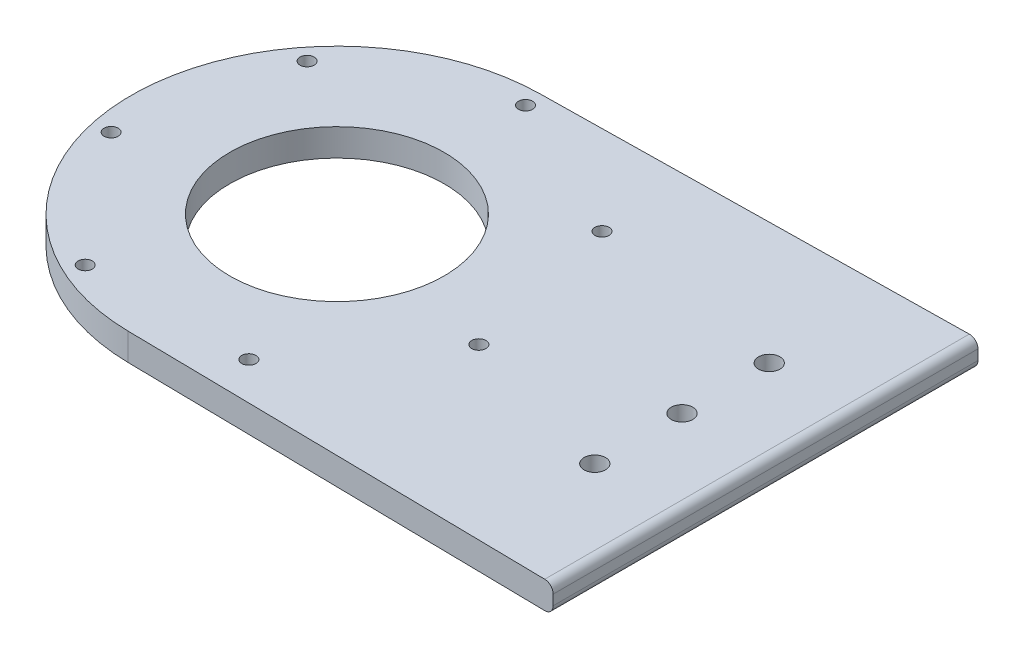
SolidWorks part; units mm, degrees
material "6061 Alloy"
ref_plane "Front Plane" through (0, 0, 0) normal (0, 0, 1) x (1, 0, 0)
ref_plane "Top Plane" through (0, 0, 0) normal (0, 1, 0) x (1, 0, 0)
ref_plane "Right Plane" through (0, 0, 0) normal (1, 0, 0) x (0, 0, -1)
ref_axis "X Axis" through (-88.99, 0, 0) along (1, 0, 0)
ref_axis "Y Axiz" through (0, 0, 55) along (0, 0, -1)
ref_axis "Z Axis" through (0, 55, 0) along (0, -1, 0)
sketch "Sketch1" plane through (0, 0, 0) normal (0, 1, 0) x (1, 0, 0)
  line L0 (0, 0) -> (10, 0) construction
  line L5 (0, 0) -> (100, 0) construction
  line L6 (100, 49.5563) -> (100, -49.5563)
  line L7 (-81.4, 0) -> (81.4, 0) construction
  line L8 (-0.7442, 47.9942) -> (100, 49.5563)
  line L9 (80.5, 20.35) -> (80.5, -20.35) construction
  line L10 (-0.7442, -47.9942) -> (100, -49.5563)
  arc A2 (-0.7442, 47.9942) -> (-0.7442, -47.9942) centre (0, 0) ccw
  circle A8 centre (0, 0) radius 25
  circle A15 centre (80.5, 20.35) radius 0.5
  circle A16 centre (80.5, -20.35) radius 0.5
  circle A19 centre (80.5, 0) radius 0.5
  point P0 (80.5, 20.35)
  point P2 (80.5, -20.35)
  point P29 (0, 0)
  dimension "D2" = 0
  dimension "D3" = 96
  dimension "D5" = 1
  dimension "D7" = 10
  dimension "D9" = 100.7442
  dimension "D10" = 50
  dimension "D13" = 1
  dimension "D14" = 1
  dimension "D4" = 100.7442
  dimension "D8" = 100
  dimension "D11" = 20.35
  dimension "D12" = 19.5
extrude "Boss-Extrude1" add sketch "Sketch1" along normal blind 6.35 contours L8 A2 L10 A8 region at (36.5027, 0, 0)
hole_wizard "M6x1.0 Tapped Hole1" positions "3DSketch1" profile "Sketch2" tap size "M6x1.0" standard "ANSI Metric"
sketch3d "3DSketch1"
  line L0 (80.5, 6.35, -20.35) -> (80.5, 0, -20.35) construction
  line L1 (80.5, 6.35, 0) -> (80.5, 0, 0) construction
  line L2 (80.5, 6.35, 20.35) -> (80.5, 0, 20.35) construction
  point P0 (80.5, 6.35, -20.35)
  point P4 (80.5, 6.35, 0)
  point P8 (80.5, 6.35, 20.35)
sketch "Sketch2" plane through (80.5, 6.35, -20.35) normal (1, 0, 0) x (0, 0, 1)
  line L0 (0, 0) -> (0, 16.5022)
  line L1 (0, 16.5022) -> (2.5, 15)
  line L2 (2.5, 15) -> (2.5, 0)
  line L5 (2.5, 0) -> (0, 0)
  line L10 (0, 16.5022) -> (-2.5, 15) construction
  line L11 (0, -6.35) -> (0, 107.95) construction
  dimension "Tap Drill Dia." = 5
  dimension "Tap Drill Depth" = 15
  dimension "Drill Angle" = 118
cosmetic thread "Hole Thread1" parameters "D1"=12, "D2"=6
cosmetic thread "Hole Thread2" parameters "D1"=12, "D2"=6
cosmetic thread "Hole Thread3" parameters "D1"=12, "D2"=6
sketch "Sketch3" plane through (0, 6.35, 0) normal (0, 1, 0) x (1, 0, 0)
  line L0 (0, 0) -> (0, 44) construction
  circle A0 centre (0, 44) radius 1.5
  circle A1 centre (34.4006, 27.4336) radius 1.5
  circle A2 centre (42.8968, -9.7909) radius 1.5
  circle A3 centre (19.0909, -39.6426) radius 1.5
  circle A4 centre (-19.0909, -39.6426) radius 1.5
  circle A5 centre (-42.8968, -9.7909) radius 1.5
  circle A6 centre (-34.4006, 27.4336) radius 1.5
  point P1 (0, 44)
  point P7 (34.4006, 27.4336)
  point P9 (42.8968, -9.7909)
  point P11 (19.0909, -39.6426)
  point P13 (-19.0909, -39.6426)
  point P15 (-42.8968, -9.7909)
  point P17 (-34.4006, 27.4336)
  dimension "D1" = 44
  dimension "D2" = 3
  dimension "D3" = 7
hole_wizard "M4x0.7 Tapped Hole1" positions "Sketch3" profile "Sketch4" tap size "M4x0.7" standard "ANSI Metric"
sketch "Sketch4" plane through (-34.4006, 6.35, -27.4336) normal (1, 0, 0) x (0, 0, 1)
  line L0 (0, 0) -> (0, 11.0914)
  line L1 (0, 11.0914) -> (1.65, 10.1)
  line L2 (1.65, 10.1) -> (1.65, 0)
  line L5 (1.65, 0) -> (0, 0)
  line L10 (0, 11.0914) -> (-1.65, 10.1) construction
  line L11 (0, -6.35) -> (0, 107.95) construction
  dimension "Tap Drill Dia." = 3.3
  dimension "Tap Drill Depth" = 10.1
  dimension "Drill Angle" = 118
cosmetic thread "Hole Thread4" parameters "D1"=8, "D2"=4
cosmetic thread "Hole Thread5" parameters "D1"=8, "D2"=4
cosmetic thread "Hole Thread6" parameters "D1"=8, "D2"=4
cosmetic thread "Hole Thread7" parameters "D1"=8, "D2"=4
cosmetic thread "Hole Thread8" parameters "D1"=8, "D2"=4
cosmetic thread "Hole Thread9" parameters "D1"=8, "D2"=4
cosmetic thread "Hole Thread10" parameters "D1"=8, "D2"=4
fillet "Fillet1" radius 2 2 edges at (100, 0, 0) (100, 6.35, 0)
